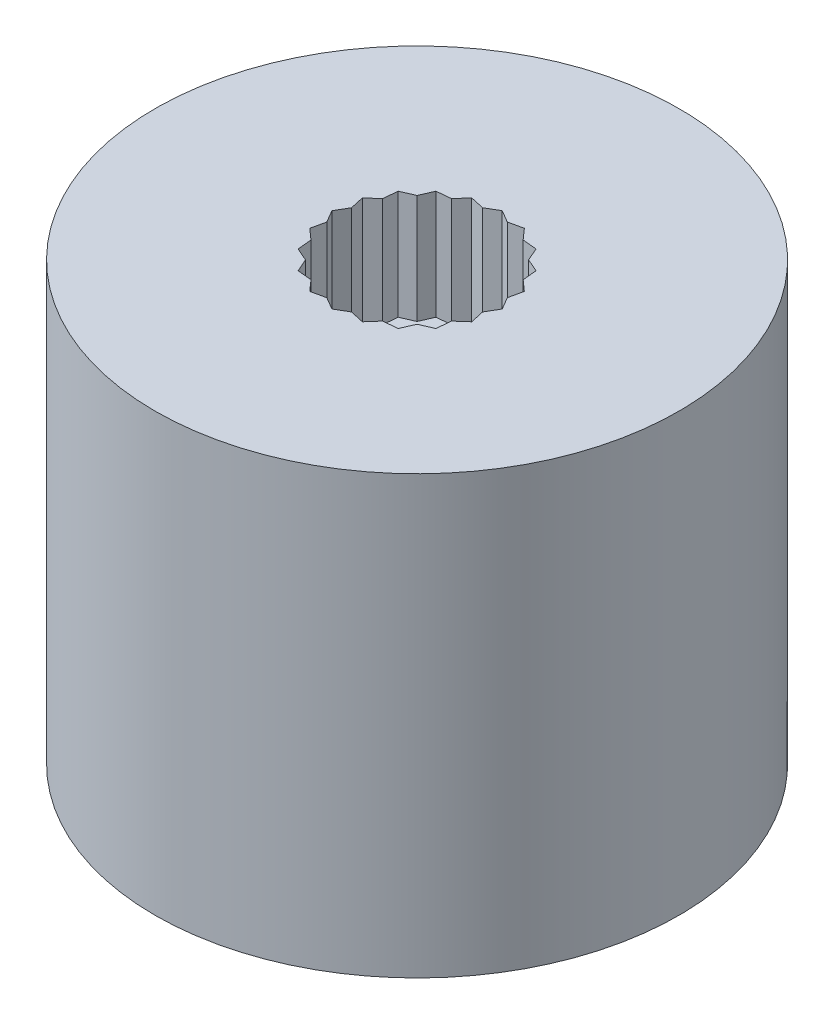
SolidWorks part; units mm, degrees
ref_plane "Front Plane" through (0, 0, 0) normal (0, 0, 1) x (1, 0, 0)
ref_plane "Top Plane" through (0, 0, 0) normal (0, 1, 0) x (1, 0, 0)
ref_plane "Right Plane" through (0, 0, 0) normal (1, 0, 0) x (0, 0, -1)
sketch "Sketch1" plane through (0, 0, 0) normal (0, 1, 0) x (1, 0, 0)
  circle A0 centre (0, 0) radius 6
  dimension "D1" = 12
extrude "Boss-Extrude1" add sketch "Sketch1" along normal blind 10
sketch "Sketch2" plane through (0, 10, 0) normal (0, 1, 0) x (1, 0, 0)
  circle A0 centre (0, 0) radius 1.8
  dimension "D1" = 3.6
extrude "Cut-Extrude1" cut sketch "Sketch2" against normal blind 2.5
sketch "Sketch3" plane through (0, 0, 0) normal (0, -1, 0) x (1, 0, 0)
  circle A0 centre (0, 0) radius 3.75
  dimension "D1" = 7.5
extrude "Cut-Extrude2" cut sketch "Sketch3" against normal blind 4.8
sketch "Sketch5" plane through (0, 0, 0) normal (0, -1, 0) x (-1, 0, 0)
  line L0 (1.0353, 3.8637) -> (1.4351, 3.4645)
  line L1 (1.4351, 3.4645) -> (2, 3.4641)
  line L2 (2, 3.4641) -> (2.2829, 2.9751)
  line L3 (2.2829, 2.9751) -> (2.8284, 2.8284)
  line L4 (2.8284, 2.8284) -> (2.9751, 2.2829)
  line L5 (2.9751, 2.2829) -> (3.4641, 2)
  line L6 (3.4641, 2) -> (3.4645, 1.4351)
  line L7 (3.4645, 1.4351) -> (3.8637, 1.0353)
  line L8 (3.8637, 1.0353) -> (3.7179, 0.4895)
  line L9 (3.7179, 0.4895) -> (4, 0)
  line L10 (4, 0) -> (3.7179, -0.4895)
  line L11 (3.7179, -0.4895) -> (3.8637, -1.0353)
  line L12 (3.8637, -1.0353) -> (3.4645, -1.4351)
  line L13 (3.4645, -1.4351) -> (3.4641, -2)
  line L14 (3.4641, -2) -> (2.9751, -2.2829)
  line L15 (2.9751, -2.2829) -> (2.8284, -2.8284)
  line L16 (2.8284, -2.8284) -> (2.2829, -2.9751)
  line L17 (2.2829, -2.9751) -> (2, -3.4641)
  line L18 (2, -3.4641) -> (1.4351, -3.4645)
  line L19 (1.4351, -3.4645) -> (1.0353, -3.8637)
  line L20 (1.0353, -3.8637) -> (0.4895, -3.7179)
  line L21 (0.4895, -3.7179) -> (0, -4)
  line L22 (0, -4) -> (-0.4895, -3.7179)
  line L23 (-0.4895, -3.7179) -> (-1.0353, -3.8637)
  line L24 (-1.0353, -3.8637) -> (-1.4351, -3.4645)
  line L25 (-1.4351, -3.4645) -> (-2, -3.4641)
  line L26 (0, 4) -> (0.4895, 3.7179)
  line L27 (0.4895, 3.7179) -> (1.0353, 3.8637)
  line L28 (-2, -3.4641) -> (-2.2829, -2.9751)
  line L29 (-2.2829, -2.9751) -> (-2.8284, -2.8284)
  line L30 (-2.8284, -2.8284) -> (-2.9751, -2.2829)
  line L31 (-2.9751, -2.2829) -> (-3.4641, -2)
  line L32 (-3.4641, -2) -> (-3.4645, -1.4351)
  line L33 (-3.4645, -1.4351) -> (-3.8637, -1.0353)
  line L34 (-3.8637, -1.0353) -> (-3.7179, -0.4895)
  line L35 (-3.7179, -0.4895) -> (-4, 0)
  line L36 (-4, 0) -> (-3.7179, 0.4895)
  line L37 (-3.7179, 0.4895) -> (-3.8637, 1.0353)
  line L38 (-3.8637, 1.0353) -> (-3.4645, 1.4351)
  line L39 (-3.4645, 1.4351) -> (-3.4641, 2)
  line L40 (-3.4641, 2) -> (-2.9751, 2.2829)
  line L41 (-2.9751, 2.2829) -> (-2.8284, 2.8284)
  line L42 (-2.8284, 2.8284) -> (-2.2829, 2.9751)
  line L43 (-2.2829, 2.9751) -> (-2, 3.4641)
  line L44 (-2, 3.4641) -> (-1.4351, 3.4645)
  line L45 (-1.4351, 3.4645) -> (-1.0353, 3.8637)
  line L46 (-1.0353, 3.8637) -> (-0.4895, 3.7179)
  line L47 (-0.4895, 3.7179) -> (0, 4)
  point P10 (-0.8092, -2.8161)
  point P14 (-1.5105, -2.5108)
  point P18 (-2.1089, -2.0343)
  point P22 (-2.5635, -1.4191)
  point P26 (-2.8435, -0.7073)
  point P30 (-2.9296, 0.0528)
  point P32 (-0.0528, -2.9296)
  point P36 (-2.8161, 0.8092)
  point P40 (-2.5108, 1.5105)
  point P44 (-2.0343, 2.1089)
  point P48 (-1.4191, 2.5635)
  point P52 (-0.7073, 2.8435)
  point P56 (0.0528, 2.9296)
  point P60 (0.8092, 2.8161)
  point P64 (1.5105, 2.5108)
  point P68 (2.1089, 2.0343)
  point P72 (2.5635, 1.4191)
  point P76 (2.8435, 0.7073)
  point P80 (2.9296, -0.0528)
  point P84 (2.8161, -0.8092)
  point P88 (2.5108, -1.5105)
  point P92 (2.0343, -2.1089)
  point P96 (1.4191, -2.5635)
  point P100 (0.7073, -2.8435)
  point P102 (0, 0)
  dimension "D1" = 24
extrude "Cut-Extrude3" cut sketch "Sketch5" against normal up to surface (4.8 mm away) up to face at (0, 4.8, -3.75)
sketch "Sketch8" plane through (0, 10, 0) normal (0, 1, 0) x (1, 0, 0)
  line L0 (0.6026, 1.8546) -> (0.82, 1.6094)
  line L1 (0.82, 1.6094) -> (1.1462, 1.5776)
  line L2 (1.1462, 1.5776) -> (1.2772, 1.2772)
  line L3 (1.2772, 1.2772) -> (1.5776, 1.1462)
  line L4 (1.5776, 1.1462) -> (1.6094, 0.82)
  line L5 (1.6094, 0.82) -> (1.8546, 0.6026)
  line L6 (1.8546, 0.6026) -> (1.784, 0.2826)
  line L7 (1.784, 0.2826) -> (1.95, 0)
  line L8 (1.95, 0) -> (1.784, -0.2826)
  line L9 (1.784, -0.2826) -> (1.8546, -0.6026)
  line L10 (1.8546, -0.6026) -> (1.6094, -0.82)
  line L11 (1.6094, -0.82) -> (1.5776, -1.1462)
  line L12 (1.5776, -1.1462) -> (1.2772, -1.2772)
  line L13 (1.2772, -1.2772) -> (1.1462, -1.5776)
  line L14 (1.1462, -1.5776) -> (0.82, -1.6094)
  line L15 (0.82, -1.6094) -> (0.6026, -1.8546)
  line L16 (0.6026, -1.8546) -> (0.2826, -1.784)
  line L17 (0.2826, -1.784) -> (0, -1.95)
  line L18 (0, -1.95) -> (-0.2826, -1.784)
  line L19 (-0.2826, -1.784) -> (-0.6026, -1.8546)
  line L20 (-0.6026, -1.8546) -> (-0.82, -1.6094)
  line L21 (-0.82, -1.6094) -> (-1.1462, -1.5776)
  line L22 (0, 1.95) -> (0.2826, 1.784)
  line L23 (0.2826, 1.784) -> (0.6026, 1.8546)
  line L24 (-1.1462, -1.5776) -> (-1.2772, -1.2772)
  line L26 (-1.2772, -1.2772) -> (-1.5776, -1.1462)
  line L27 (-1.5776, -1.1462) -> (-1.6094, -0.82)
  line L28 (-1.6094, -0.82) -> (-1.8546, -0.6026)
  line L29 (-1.8546, -0.6026) -> (-1.784, -0.2826)
  line L30 (-1.784, -0.2826) -> (-1.95, 0)
  line L31 (-1.95, 0) -> (-1.784, 0.2826)
  line L32 (-1.784, 0.2826) -> (-1.8546, 0.6026)
  line L33 (-1.8546, 0.6026) -> (-1.6094, 0.82)
  line L34 (-1.6094, 0.82) -> (-1.5776, 1.1462)
  line L35 (-1.5776, 1.1462) -> (-1.2772, 1.2772)
  line L36 (-1.2772, 1.2772) -> (-1.1462, 1.5776)
  line L37 (-1.1462, 1.5776) -> (-0.82, 1.6094)
  line L38 (-0.82, 1.6094) -> (-0.6026, 1.8546)
  line L39 (-0.6026, 1.8546) -> (-0.2826, 1.784)
  line L40 (-0.2826, 1.784) -> (0, 1.95)
  circle A1 centre (0, 0) radius 1.8062 construction
  point P28 (0, 0)
  point P69 (0, 0)
  dimension "D1" = 20
extrude "Cut-Extrude4" cut sketch "Sketch8" against normal up to surface (2.5 mm away) up to face at (0, 7.5, 1.8)
sketch "Sketch9" plane through (0, 4.8, 0) normal (0, -1, 0) x (1, 0, 0)
  circle A0 centre (0, 0) radius 2
extrude "Cut-Extrude5" cut sketch "Sketch9" against normal blind 1.5
sketch "Sketch10" plane through (0, 6.3, 0) normal (0, -1, 0) x (1, 0, 0)
  circle A0 centre (0, 0) radius 1
extrude "Cut-Extrude6" cut sketch "Sketch10" against normal blind 4
